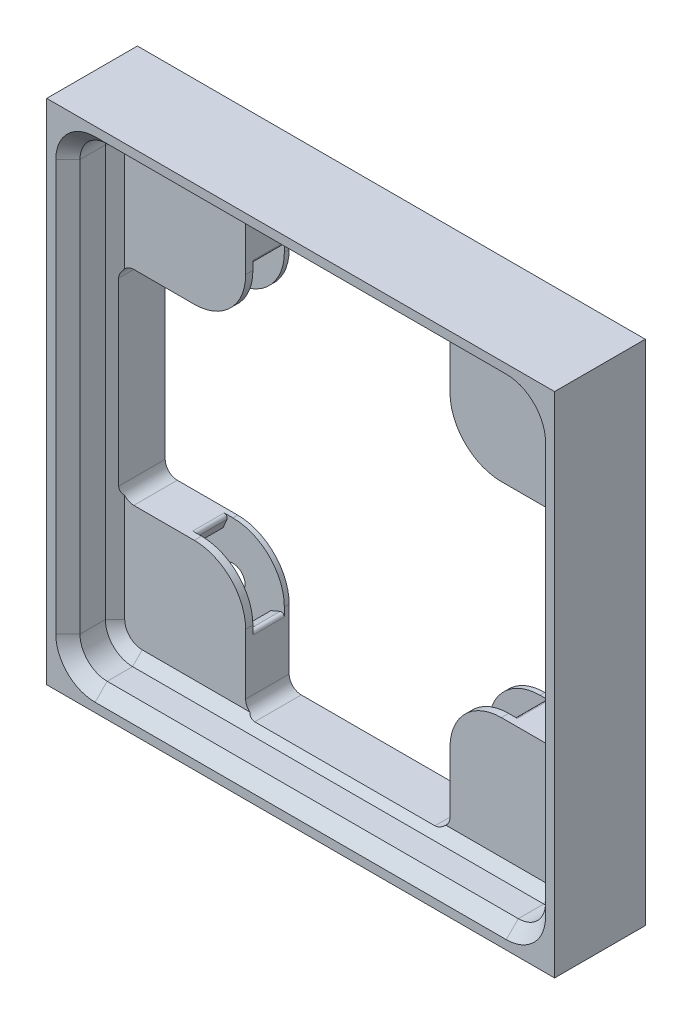
SolidWorks part; units mm, degrees
ref_plane "Front Plane" through (0, 0, 0) normal (0, 0, 1) x (1, 0, 0)
ref_plane "Top Plane" through (0, 0, 0) normal (0, 1, 0) x (1, 0, 0)
ref_plane "Right Plane" through (0, 0, 0) normal (1, 0, 0) x (0, 0, -1)
sketch "Sketch1" plane through (0, 0, 0) normal (0, 0, 1) x (1, 0, 0)
  line L0 (-21, 21) -> (0, 0) construction
  line L1 (-21, 0) -> (-18.7, 0)
  line L2 (-21, 0) -> (-21, 21)
  line L3 (-21, 21) -> (0, 21)
  line L5 (-13.5132, 9.5534) -> (-9.5534, 13.5132) construction
  line L6 (-10.4019, 14.9981) -> (-8.45, 13.0462) construction
  line L7 (-14.9981, 10.4019) -> (-13.0462, 8.45) construction
  line L8 (-13.4235, 8.45) -> (-18.7, 8.45)
  line L9 (-8.45, 13.4235) -> (-8.45, 18.7)
  line L10 (-9.5534, 13.5132) -> (-8.7974, 13.1932)
  line L11 (-13.5132, 9.5534) -> (-13.1932, 8.7974)
  line L12 (0, 18.7) -> (0, 21)
  line L13 (-8.45, 18.7) -> (0, 18.7)
  line L16 (-18.7, 0) -> (-18.7, 8.45)
  line L17 (-18.7, 18.7) -> (-2.3, 18.7) construction
  line L18 (-18.7, 2.3) -> (-18.7, 18.7) construction
  line L19 (-2.3, 2.3) -> (-2.3, 18.7) construction
  line L20 (-18.7, 2.3) -> (-2.3, 2.3) construction
  line L21 (0, 0) -> (0, 21) construction
  line L22 (-21, 0) -> (0, 0) construction
  arc A0 (-9.5534, 13.5132) -> (-13.5132, 9.5534) centre (-12.7, 12.7) ccw
  arc A2 (-13.4235, 8.45) -> (-13.1932, 8.7974) centre (-13.4235, 8.7) ccw
  arc A3 (-8.45, 13.4235) -> (-8.7974, 13.1932) centre (-8.7, 13.4235) cw
  circle A4 centre (-12.7, 12.7) radius 4.25 construction
  point P11 (-11.5333, 11.5333)
  dimension "D3" = 6.5
  dimension "D2" = 0.25
  dimension "D8" = 8.5
  dimension "D1" = 21
  dimension "D4" = 8.3
  dimension "D5" = 8.3
  dimension "D6" = 5.6
  dimension "D7" = 2.3
extrude "Magnet Slot" add sketch "Sketch1" along normal blind 2.6
sketch "Sketch2" plane through (0, 0, 2.6) normal (0, 0, 1) x (1, 0, 0)
  line L0 (-8.7974, 13.1932) -> (-9.5534, 13.5132)
  line L2 (-13.5132, 9.5534) -> (-13.1932, 8.7974)
  line L4 (-13.4235, 8.45) -> (-18.7, 8.45)
  line L5 (-12.7, 8.45) -> (-18.7, 8.45)
  line L6 (-18.7, 8.45) -> (-18.7, 0)
  line L7 (-18.7, 8.45) -> (-18.7, 0)
  line L8 (-18.7, 0) -> (-21, 0)
  line L9 (-18.7, 0) -> (-21, 0)
  line L10 (-21, 0) -> (-21, 21)
  line L11 (-21, 0) -> (-21, 21)
  line L12 (-21, 21) -> (0, 21)
  line L13 (-21, 21) -> (0, 21)
  line L14 (0, 21) -> (0, 18.7)
  line L15 (0, 21) -> (0, 18.7)
  line L16 (0, 18.7) -> (-8.45, 18.7)
  line L17 (0, 18.7) -> (-8.45, 18.7)
  line L18 (-8.45, 18.7) -> (-8.45, 13.4235)
  line L19 (-8.45, 18.7) -> (-8.45, 12.7)
  arc A0 (-9.5534, 13.5132) -> (-13.5132, 9.5534) centre (-12.7, 12.7) ccw
  arc A2 (-13.4235, 8.45) -> (-13.1932, 8.7974) centre (-13.4235, 8.7) ccw
  arc A4 (-8.7974, 13.1932) -> (-8.45, 13.4235) centre (-8.7, 13.4235) ccw
  arc A6 (-12.7, 8.45) -> (-8.45, 12.7) centre (-12.7, 12.7) ccw
  dimension "D1" = 8.5
extrude "Magnet Topper" add sketch "Sketch2" along normal blind 0.6
sketch "Sketch3" plane through (0, 0, 0) normal (0, 0, -1) x (-1, 0, 0)
  line L8 (18.7, 8.45) -> (18.7, 0)
  line L9 (12.7, 8.45) -> (18.7, 8.45)
  line L10 (8.45, 18.7) -> (8.45, 12.7)
  line L11 (0, 18.7) -> (8.45, 18.7)
  line L12 (0, 21) -> (0, 18.7)
  line L13 (21, 21) -> (0, 21)
  line L14 (21, 0) -> (21, 21)
  line L15 (18.7, 0) -> (21, 0)
  line L16 (18.7, 8.45) -> (18.7, 0)
  line L17 (12.7, 8.45) -> (18.7, 8.45)
  line L18 (8.45, 18.7) -> (8.45, 12.7)
  line L19 (0, 18.7) -> (8.45, 18.7)
  line L20 (0, 21) -> (0, 18.7)
  line L21 (21, 21) -> (0, 21)
  line L22 (21, 0) -> (21, 21)
  line L23 (18.7, 0) -> (21, 0)
  arc A1 (8.45, 12.7) -> (12.7, 8.45) centre (12.7, 12.7) ccw
  arc A2 (8.45, 12.7) -> (12.7, 8.45) centre (12.7, 12.7) ccw
  dimension "D1" = 0
extrude "Bottom" add sketch "Sketch3" along normal blind 0.4
sketch "Sketch4" plane through (0, 0, -0.4) normal (0, 0, -1) x (-1, 0, 0)
  line L0 (12.7, 12.7) -> (21, 21) construction
  line L1 (21, 21) -> (0, 21) construction
  line L2 (21, 0) -> (21, 21) construction
  line L3 (12.7, 12.7) -> (16.2355, 16.2355) construction
  line L4 (11.9929, 13.4071) -> (15.5284, 16.9426)
  line L5 (13.4071, 11.9929) -> (16.9426, 15.5284)
  arc A0 (13.5132, 9.5534) -> (9.5534, 13.5132) centre (12.7, 12.7) ccw construction
  arc A1 (13.5132, 9.5534) -> (9.5534, 13.5132) centre (12.7, 12.7) ccw construction
  arc A2 (11.9929, 13.4071) -> (13.4071, 11.9929) centre (12.7, 12.7) ccw
  arc A3 (16.9426, 15.5284) -> (15.5284, 16.9426) centre (16.2355, 16.2355) ccw
  point P3 (14.4678, 14.4678)
  dimension "D1" = 5
extrude "Cut-Extrude1" cut sketch "Sketch4" against normal up to surface (3 mm away) up to face at (-11.3138, 11.3138, 2.6)
fillet "Fillet1" radius 1 2 edges at (-8.45, 18.7, 1.4) (-18.7, 8.45, 1.4)
sketch "Sketch5" plane through (0, 0, 3.2) normal (0, 0, 1) x (1, 0, 0)
  line L0 (0, 21) -> (-17.25, 21)
  line L1 (-21, 17.25) -> (-21, 0)
  line L2 (0, 19.25) -> (-17, 19.25)
  line L3 (-19.25, 17) -> (-19.25, 0)
  line L4 (-21, 0) -> (-19.25, 0)
  line L5 (0, 21) -> (0, 19.25)
  line L6 (0, 19.25) -> (-19.25, 19.25) construction
  line L7 (-19.25, 19.25) -> (-19.25, 0) construction
  line L8 (0, 21) -> (-21, 21) construction
  line L9 (-21, 21) -> (-21, 0) construction
  line L10 (-17.25, 21) -> (-21, 21)
  line L11 (-21, 21) -> (-21, 17.25)
  arc A0 (-17, 19.25) -> (-19.25, 17) centre (-17, 17) ccw
  point P15 (-21, 21)
  dimension "D2" = 2.25
  dimension "D1" = 1.75
extrude "Boss-Extrude1" add sketch "Sketch5" along normal blind 3.9
chamfer "Chamfer1" distance 0.8 angle 45 3 edges at (-19.25, 8.5, 3.2) (-18.591, 18.591, 3.2) (-8.5, 19.25, 3.2)
chamfer "Chamfer2" distance 1 angle 45 3 edges at (-8.5, 19.25, 7.1) (-18.591, 18.591, 7.1) (-19.25, 8.5, 7.1)
ref_axis "Center Axis" through (0, 0, 0) along (0, 0, 1)
pattern_circular "CirPattern1" count 4 over 360 about axis through (0, 0, 0) along (0, 0, 1) of bodies 105
combine bodies "Combine1" bodies to combine 105 108 106 107
